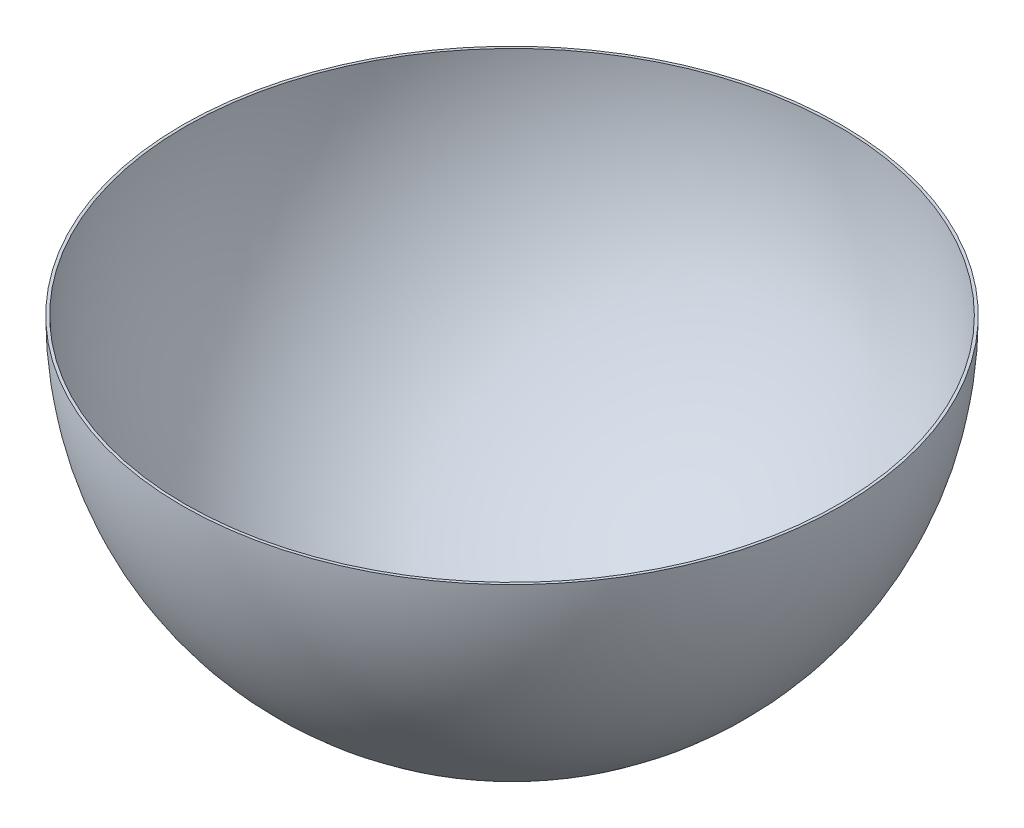
SolidWorks part; units mm, degrees
ref_plane "Front Plane" through (0, 0, 0) normal (0, 0, 1) x (1, 0, 0)
ref_plane "Top Plane" through (0, 0, 0) normal (0, 1, 0) x (1, 0, 0)
ref_plane "Right Plane" through (0, 0, 0) normal (1, 0, 0) x (0, 0, -1)
sketch "Sketch1" plane through (0, 0, 0) normal (0, 1, 0) x (1, 0, 0)
  line L0 (0, -226.695) -> (0, 226.695) construction
  line L1 (0, 226.695) -> (0, 228.6)
  line L2 (0, -226.695) -> (0, -228.6)
  arc A0 (0, 226.695) -> (0, -226.695) centre (0, 0) cw
  arc A1 (0, 228.6) -> (0, -228.6) centre (0, 0) cw
  dimension "D1" = 453.39
  dimension "D2" = 226.695
  dimension "D3" = 1.905
  dimension "D4" = 1.905
revolve "Revolve1" add sketch "Sketch1" angle 180 about L0 region at (5.1117, 0, -227.6475)
ref_plane "Plane1" through (0, -228.6, 0) normal (0, -1, 0) x (-1, 0, 0)
sketch "Sketch2" plane through (0, -228.6, 0) normal (0, -1, 0) x (-1, 0, 0)
  circle A0 centre (0, 0) radius 6.35
  dimension "D1" = 12.7
extrude "Cut-Extrude1" cut sketch "Sketch2" against normal through all
